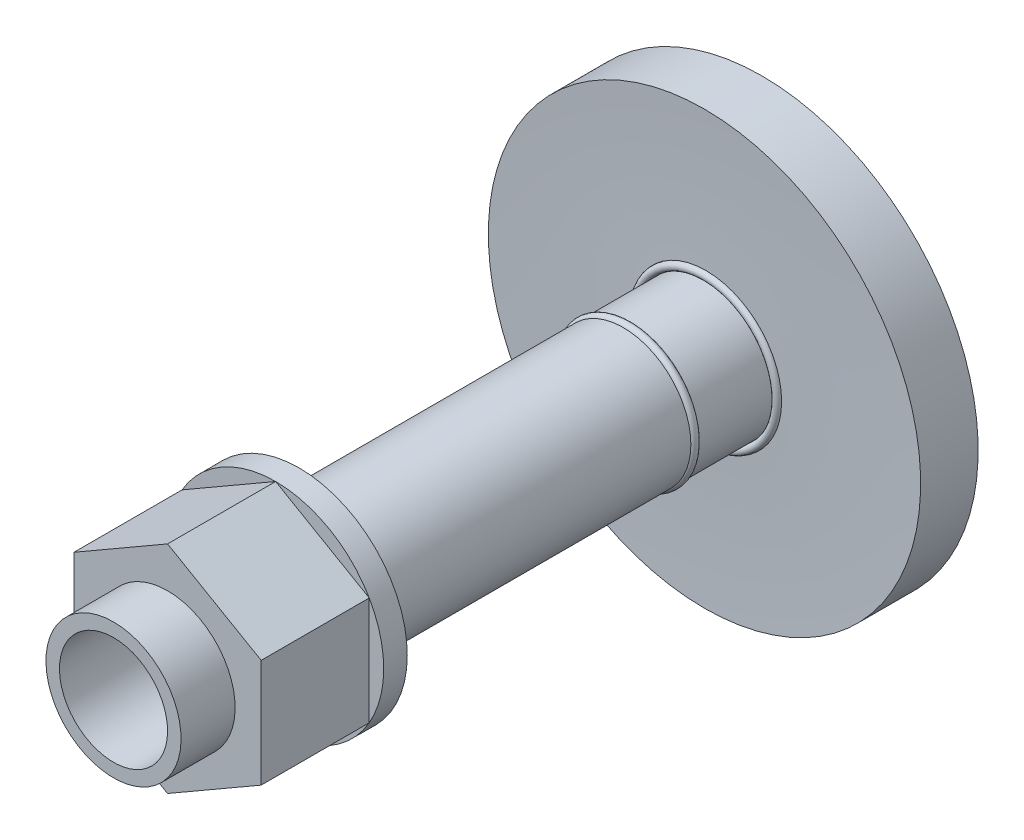
SolidWorks part; units mm, degrees
ref_plane "Front Plane" through (0, 0, 0) normal (0, 0, 1) x (1, 0, 0)
ref_plane "Top Plane" through (0, 0, 0) normal (0, 1, 0) x (1, 0, 0)
ref_plane "Right Plane" through (0, 0, 0) normal (1, 0, 0) x (0, 0, -1)
sketch "Sketch1" plane through (0, 0, 0) normal (1, 0, 0) x (0, 0, -1)
  line L0 (93.2584, 0) -> (-250, 0) construction
  line L1 (-126.7416, 20) -> (-126.7416, 40)
  line L2 (-126.7416, 40) -> (-78.0303, 40)
  line L4 (-76.7416, 25) -> (43.2584, 25)
  line L5 (93.2584, 20) -> (-126.7416, 20)
  line L6 (93.2584, 0.7576) -> (93.2584, 0)
  line L8 (93.2584, 80) -> (93.2584, 20)
  line L9 (93.2584, 0) -> (93.2584, 0.7576)
  line L11 (71.9697, 80) -> (93.2584, 80)
  line L13 (43.2584, 25) -> (72.4575, 25)
  line L14 (-126.7416, 25) -> (-146.7416, 25)
  line L15 (-146.7416, 25) -> (-146.7416, 20)
  line L16 (-146.7416, 20) -> (-126.7416, 20)
  arc A0 (-76.7416, 25) -> (-78.0303, 40) centre (-954.1241, -42.8235) ccw
  arc A2 (72.4575, 25) -> (71.9697, 80) centre (-927.3689, 43.6351) ccw
  dimension "D7" = 1760
  dimension "D2" = 25
  dimension "D3" = 80
  dimension "D4" = 40
  dimension "D5" = 20
  dimension "D1" = 50
  dimension "D6" = 50
  dimension "D8" = 20
  dimension "D9" = 120
revolve "Revolve1" add sketch "Sketch1" angle 360 about L0 region at (0, 22.5, 136.7416) region at (0, 22.5, 124.4613)
sketch "Sketch2" plane through (0, 0, 126.7416) normal (0, 0, 1) x (1, 0, 0)
  line L0 (0, 0) -> (38.5975, 0) construction
  line L1 (34.641, -20) -> (34.641, 20)
  line L2 (34.641, 20) -> (0, 40)
  line L3 (0, 40) -> (-34.641, 20)
  line L4 (-34.641, 20) -> (-34.641, -20)
  line L5 (-34.641, -20) -> (0, -40)
  line L6 (0, -40) -> (34.641, -20)
  line L7 (0, 0) -> (34.641, 20) construction
  circle A0 centre (0, 0) radius 34.641 construction
  circle A1 centre (0, 0) radius 47.4757
  dimension "D1" = 30
extrude "Cut-Extrude1" cut sketch "Sketch2" against normal blind 40
sketch "Sketch3" plane through (0, 0, 0) normal (0, 1, 0) x (1, 0, 0)
  line L0 (80, 71.9697) -> (-80, 71.9697) construction
  line L1 (25, 71.9697) -> (28, 71.9697)
  line L2 (25, 71.9697) -> (25, 73.9697)
  line L3 (25, 73.9697) -> (28, 73.9697)
  line L4 (28, 71.9697) -> (28, 73.9697)
  line L5 (25, -76.7416) -> (25, 72.4575) construction
  line L6 (0, 0) -> (0, 145.935) construction
  line L8 (25, 44.9306) -> (23, 44.9306)
  line L9 (25, 44.9306) -> (25, 41.9306)
  line L10 (25, 41.9306) -> (23, 41.9306)
  line L11 (23, 44.9306) -> (23, 41.9306)
  line L12 (25, -76.7416) -> (28, -76.7416)
  line L13 (25, -76.7416) -> (25, -78.7416)
  line L14 (25, -78.7416) -> (28, -78.7416)
  line L15 (28, -76.7416) -> (28, -78.7416)
  dimension "D1" = 2
  dimension "D2" = 3
  dimension "D3" = 2
  dimension "D4" = 3
  dimension "D5" = 2
  dimension "D6" = 3
revolve "Cut-Revolve1" cut sketch "Sketch3" angle 360 about L6
sketch "Sketch4" plane through (0, 0, 0) normal (0, 1, 0) x (1, 0, 0)
  line L0 (0, 154.6414) -> (0, -221.434) construction
  line L2 (19.9988, -90.7059) -> (21.9988, -90.7059)
  line L3 (19.9988, -90.7059) -> (19.9988, -93.7059)
  line L4 (19.9988, -93.7059) -> (21.9988, -93.7059)
  line L5 (21.9988, -90.7059) -> (21.9988, -93.7059)
  line L6 (19.9988, 87.725) -> (21.9988, 87.725)
  line L7 (19.9988, 87.725) -> (19.9988, 84.725)
  line L8 (19.9988, 84.725) -> (21.9988, 84.725)
  line L9 (21.9988, 87.725) -> (21.9988, 84.725)
  dimension "D1" = 2
  dimension "D2" = 3
  dimension "D3" = 2
  dimension "D4" = 3
revolve "Cut-Revolve2" cut sketch "Sketch4" angle 360 about L0
sketch "Sketch5" plane through (0, 0, 0) normal (0, 1, 0) x (1, 0, 0)
  line L0 (-28, 72.5089) -> (28, 72.5089) construction
  line L2 (0, 162.7228) -> (0, -163.8507) construction
  circle A0 centre (24.5, 43.4306) radius 1.5
  circle A1 centre (26.5032, 72.5089) radius 1.4649
  circle A2 centre (20.4923, 86.2421) radius 1.4
  circle A3 centre (26.5032, -77.2648) radius 1.4388
  circle A4 centre (20.4923, -92.2495) radius 1.4
  dimension "D1" = 2.8
  dimension "D2" = 2.8
revolve "Revolve2" add sketch "Sketch5" angle 360 about L2
equation "\"mountAngle\" = 30deg"
equation "\"ThrusterDim\"= 140mm"
equation "\"hatchHoleDiameter\"= 600mm"
equation "\"hullThickness\"= 120mm"
equation "\"gasketHullInterconnectWidth\"= 100mm"
equation "\"collarThickness\"= 15"
equation "\"hatchTunnelLength\"=200"
equation "\"oRingDiameter\"=2"
equation "\"boltPatternRadiusInterconnect\"=500"
equation "\"interconnectBoltDiameter\"=30"
equation "\"hatchShaftDiameter\"=20"
equation "\"hatchMinima\"=50"
equation "\"hullDiameter\"=2000"
equation "\"hatchMaxima\"=180"
equation "\"bushingFlatHatch\"=15"
equation "\"hingePivotDiameter\"=20"
equation "\"handleWidth\"=250"
equation "\"handleHeight\"=160"
equation "\"handleThickness\"=25"
equation "\"FrameLength\"= 4300"
equation "\"FrameMidLength\"= 3000"
equation "\"TubeOD\"= 100"
equation "\"FrameBackFlat\"= 800"
equation "\"TubeWall\"=15"
equation "\"TopMemberAngle\"=120"
equation "\"FrameHight\"= 2500"
equation "\"D7@Sketch1\"=\"hullDiameter\" - \"hullThickness\" *2"
equation "\"D9@Sketch1\"=\"hullThickness\""
